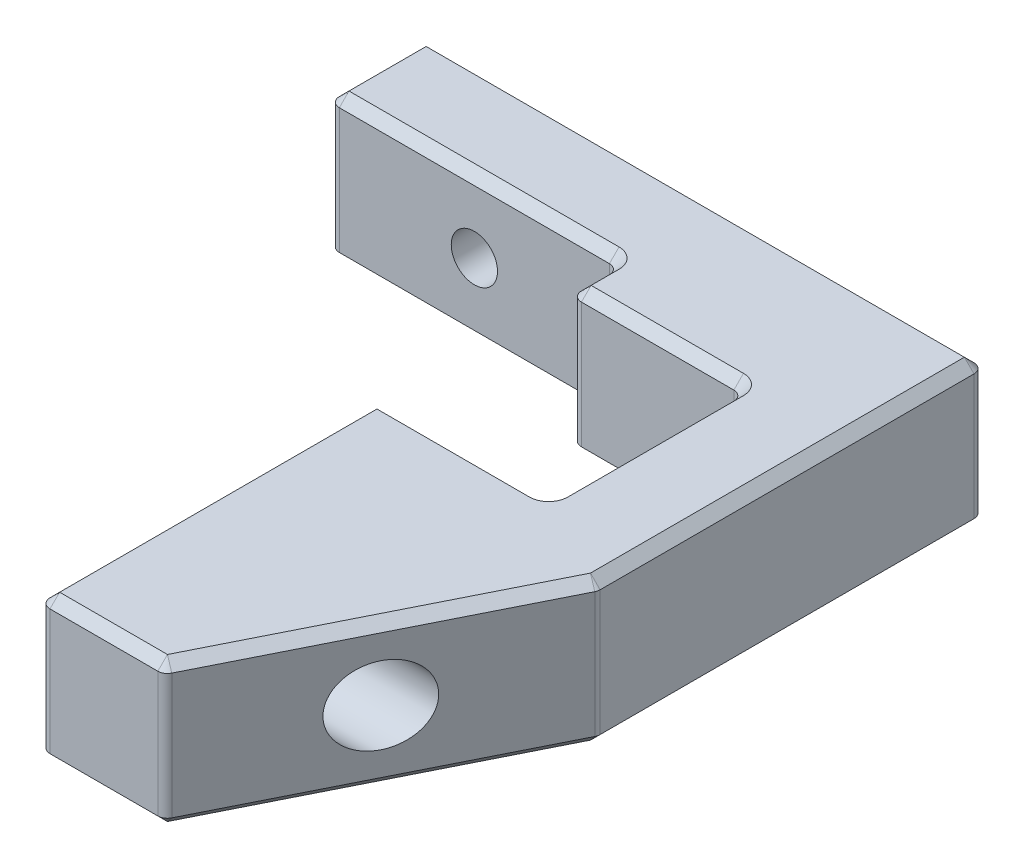
SolidWorks part; units mm, degrees
material "ABS"
ref_plane "Front Plane" through (0, 0, 0) normal (0, 0, 1) x (1, 0, 0)
ref_plane "Top Plane" through (0, 0, 0) normal (0, 1, 0) x (1, 0, 0)
ref_plane "Right Plane" through (0, 0, 0) normal (1, 0, 0) x (0, 0, -1)
sketch "Sketch2" plane through (0, 0, 0) normal (0, 1, 0) x (1, 0, 0)
  line L0 (0, 0) -> (0, 70)
  line L1 (0, 70) -> (-57.8, 70)
  line L2 (-57.8, 70) -> (-57.8, 60)
  line L3 (-57.8, 60) -> (-27.8, 60)
  line L4 (-27.8, 60) -> (-27.8, 55.1)
  line L5 (-27.8, 55.1) -> (-10, 55.1)
  line L6 (-10, 55.1) -> (-10, 34.9)
  line L7 (-10, 34.9) -> (-27.8, 34.9)
  line L8 (-27.8, 34.9) -> (-27.8, 0)
  line L9 (-27.8, 0) -> (0, 0)
  line L10 (-10, 45) -> (-27.8, 45) construction
  point P0 (0, 0)
  point P16 (-29.7424, 22.5924)
  point P17 (-27.7212, 45)
  point P18 (0, 0)
  dimension "D1" = 30
  dimension "D2" = 17.8
  dimension "D3" = 15
  dimension "D4" = 60
  dimension "D5" = 10
  dimension "D6" = 20.2
  dimension "D7" = 10
extrude "Boss-Extrude1" add sketch "Sketch2" along normal mid plane 15
hole_wizard "CBORE for M4 Hex Socket Head Cap Screw1" positions "Sketch3" profile "Sketch4" counterbore size "M4" standard "DIN" end condition up to next
sketch "Sketch3" plane through (0, 0, 0) normal (1, 0, 0) x (0, 0, -1)
  line L0 (0, 0) -> (15, 0) construction
  point P0 (15, 0)
  dimension "D1" = 15
sketch "Sketch4" plane through (0, 0, -15) normal (0, 1, 0) x (0, 0, -1)
  line L0 (0, 0) -> (0, 27.8)
  line L1 (0, 27.8) -> (2.4, 27.8)
  line L3 (2.4, 27.8) -> (2.4, 22)
  line L4 (4, 22) -> (2.4, 22)
  line L5 (4, 22) -> (4, 0.025)
  line L6 (4, 0.025) -> (4.025, 0)
  line L7 (4.025, 0) -> (0, 0)
  line L8 (-4, 0.025) -> (-4.025, 0) construction
  line L11 (0, -6.35) -> (0, 107.95) construction
  dimension "Thru Hole Dia." = 4.8
  dimension "Thru Hole Depth" = 27.8
  dimension "C'Bore Dia." = 8
  dimension "C'Bore Depth" = 22
  dimension "Near C'Sink Dia." = 8.05
  dimension "Near C'Sink Angle" = 90
hole_wizard "CBORE for M4 Hex Socket Head Cap Screw2" positions "Sketch7" profile "Sketch8" counterbore size "M4" standard "DIN" end condition up to next
sketch "Sketch7" plane through (0, 0, -70) normal (0, 0, -1) x (-1, 0, 0)
  line L0 (42.8, 0) -> (57.8, 0) construction
  line L1 (57.8, 7.5) -> (57.8, -7.5) construction
  point P0 (42.8, 0)
  dimension "D1" = 15
sketch "Sketch8" plane through (-42.8, 0, -70) normal (1, 0, 0) x (0, 1, 0)
  line L0 (0, 0) -> (0, 10)
  line L1 (0, 10) -> (2.4, 10)
  line L3 (2.4, 10) -> (2.4, 4.4)
  line L4 (2.4, 4.4) -> (4, 4.4)
  line L5 (4, 4.4) -> (4, 0)
  line L7 (4, 0) -> (0, 0)
  line L11 (0, -6.35) -> (0, 107.95) construction
  dimension "Thru Hole Dia." = 4.8
  dimension "Thru Hole Depth" = 10
  dimension "C'Bore Dia." = 8
  dimension "C'Bore Depth" = 4.4
chamfer "Chamfer1" distance 15 distance2 30 1 edges at (0, 0, 0) first distance on face at (-13.9, 0, 0)
fillet "Fillet1" radius 1 11 edges at (-57.8, 0, -70) (0, 0, -70) (0, 0, -30) (-15, 0, 0) (-27.8, 0, 0) (-57.8, 0, -60) (-27.8, 0, -34.9) (-27.8, 0, -55.1) (-10, 0, -34.9) (-10, 0, -55.1) (-27.8, 0, -60)
chamfer "Chamfer2" distance 1 angle 45 44 edges at (-0.2929, 7.5, -69.7071) (0, 7.5, -49.618) (-0.0268, 7.5, -30.0063) (-7.4146, 7.5, -15.1708) (-15.0923, 7.5, -0.1493) (-21.209, 7.5, 0) (-27.5071, 7.5, -0.2929) (-27.8, 7.5, -17.45) (-27.5071, 7.5, -34.6071) (-18.9, 7.5, -34.9) (-10.2929, 7.5, -35.1929) (-10, 7.5, -45) (-10.2929, 7.5, -54.8071) (-18.9, 7.5, -55.1) (-27.5071, 7.5, -55.3929) (-27.8, 7.5, -57.55) (-28.0929, 7.5, -59.7071) (-42.8, 7.5, -60) (-57.5071, 7.5, -60.2929) (-57.8, 7.5, -65) (-57.5071, 7.5, -69.7071) (-28.9, 7.5, -70) (-57.5071, -7.5, -60.2929) (-42.8, -7.5, -60) (-28.0929, -7.5, -59.7071) (-27.8, -7.5, -57.55) (-27.5071, -7.5, -55.3929) (-18.9, -7.5, -55.1) (-10.2929, -7.5, -54.8071) (-10, -7.5, -45) (-10.2929, -7.5, -35.1929) (-18.9, -7.5, -34.9) (-27.5071, -7.5, -34.6071) (-27.8, -7.5, -17.45) (-27.5071, -7.5, -0.2929) (-21.209, -7.5, 0) (-15.0923, -7.5, -0.1493) (-7.4146, -7.5, -15.1708) (-0.0268, -7.5, -30.0063) (0, -7.5, -49.618) (-0.2929, -7.5, -69.7071) (-28.9, -7.5, -70) (-57.5071, -7.5, -69.7071) (-57.8, -7.5, -65)
